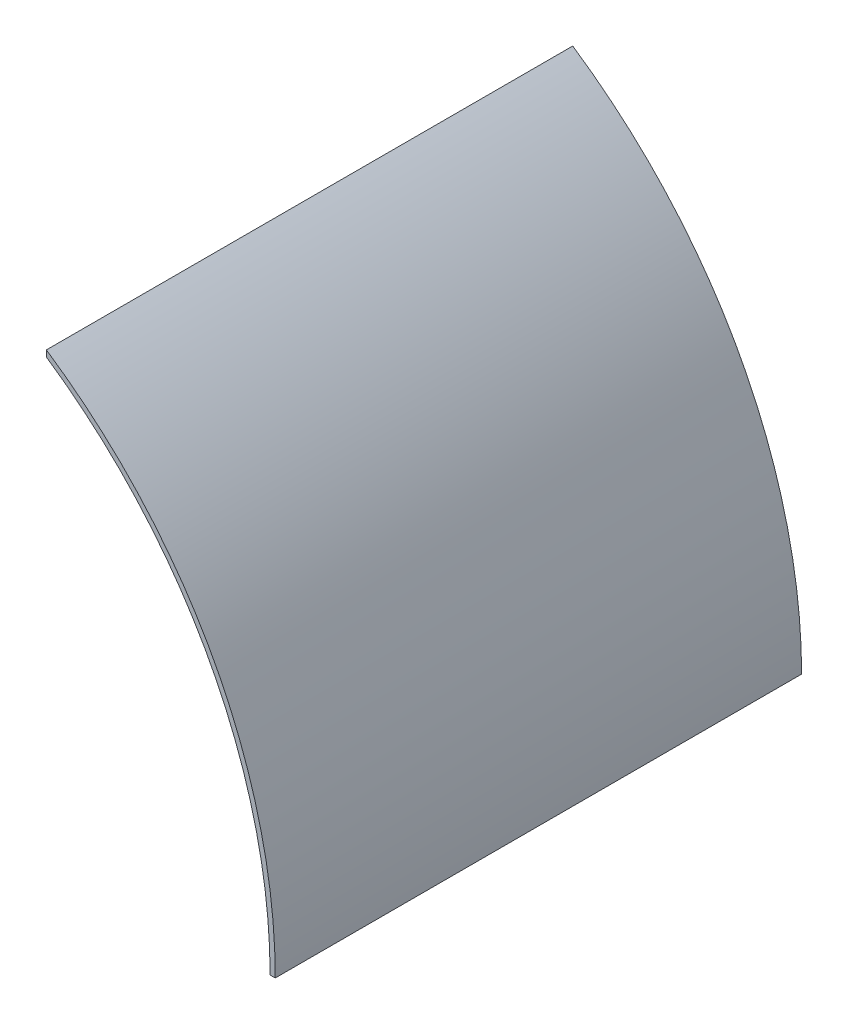
SolidWorks part; units mm, degrees
material "201 Annealed Stainless Steel (SS)"
ref_plane "Front Plane" through (0, 0, 0) normal (0, 0, 1) x (1, 0, 0)
ref_plane "Top Plane" through (0, 0, 0) normal (0, 1, 0) x (1, 0, 0)
ref_plane "Right Plane" through (0, 0, 0) normal (1, 0, 0) x (0, 0, -1)
sketch "Sketch2" plane through (0, 0, 0) normal (0, 0, 1) x (1, 0, 0)
  line L0 (-150.8811, 0) -> (150.8811, 0) construction
  line L1 (0, 150.8811) -> (0, -152.4) construction
  line L2 (85, 0) -> (85, 108.9269) construction
  line L7 (85, 126.4941) -> (85, 124.6599)
  line L8 (0, -152.4) -> (0, -160.382) construction
  line L21 (150.8811, 0) -> (152.4, 0)
  circle A0 centre (0, 0) radius 150.8811 construction
  circle A1 centre (0, 0) radius 152.4 construction
  arc A2 (85, 124.6599) -> (150.8811, 0) centre (0, 0) cw
  arc A3 (152.4, 0) -> (85, 126.4941) centre (0, 0) ccw
  dimension "D1" = 301.7622
  dimension "D2" = 304.8
  dimension "D3" = 85
extrude "Inner Ring - Right Side" add sketch "Sketch2" along normal blind 155
